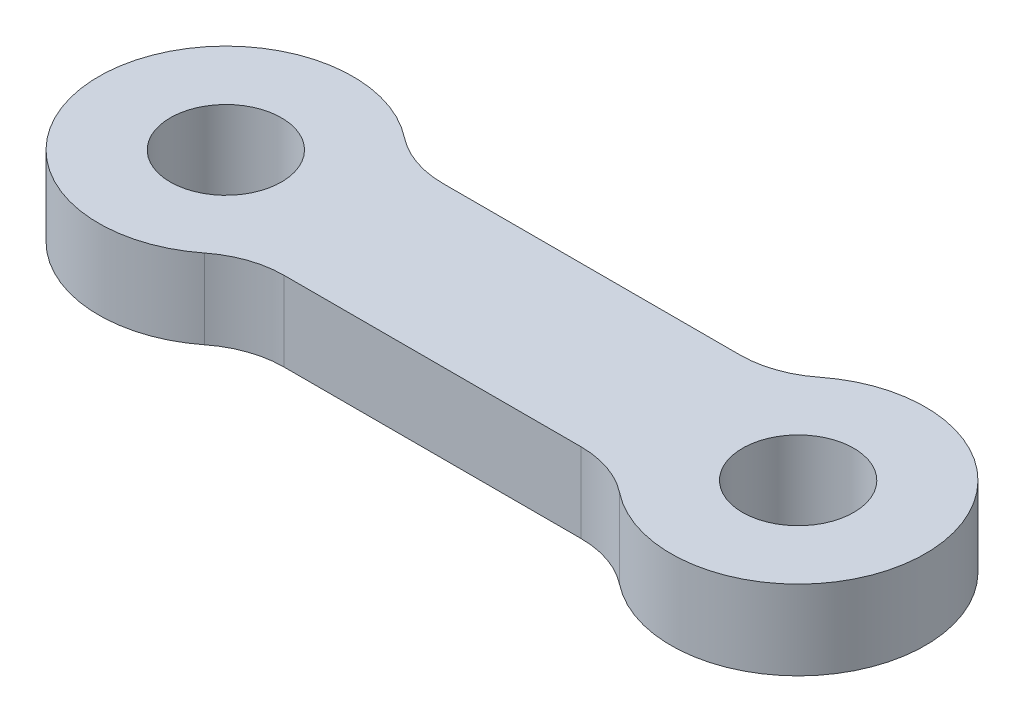
SolidWorks part; units mm, degrees
ref_plane "Front Plane" through (0, 0, 0) normal (0, 0, 1) x (1, 0, 0)
ref_plane "Top Plane" through (0, 0, 0) normal (0, 1, 0) x (1, 0, 0)
ref_plane "Right Plane" through (0, 0, 0) normal (1, 0, 0) x (0, 0, -1)
sketch "Sketch1" plane through (0, 0, 0) normal (0, 1, 0) x (1, 0, 0)
  line L0 (0, 0) -> (18, 0) construction
  line L1 (3.1225, 2.5) -> (14.8775, 2.5)
  line L2 (3.1225, -2.5) -> (14.8775, -2.5)
  circle A0 centre (0, 0) radius 4
  circle A1 centre (18, 0) radius 4
  circle A2 centre (0, 0) radius 1.75
  circle A3 centre (18, 0) radius 1.75
  dimension "D1" = 8
  dimension "D3" = 8
  dimension "D5" = 3.5
  dimension "D6" = 3.5
  dimension "D2" = 18
  dimension "D4" = 2.5
extrude "Boss-Extrude1" add sketch "Sketch1" along normal blind 2.5 contours A2 A0 | L0 A0 L2 A1 | A0 L0 A1 L1 | A1 A3 region at (3.6675, 0, 1.2873) region at (9, 0, -1.2837) region at (9, 0, 1.2837) region at (14.3325, 0, -1.2873)
fillet "Fillet1" radius 3 4 edges at (3.1225, 1.25, 2.5) (14.8775, 1.25, 2.5) (14.8775, 1.25, -2.5) (3.1225, 1.25, -2.5)
